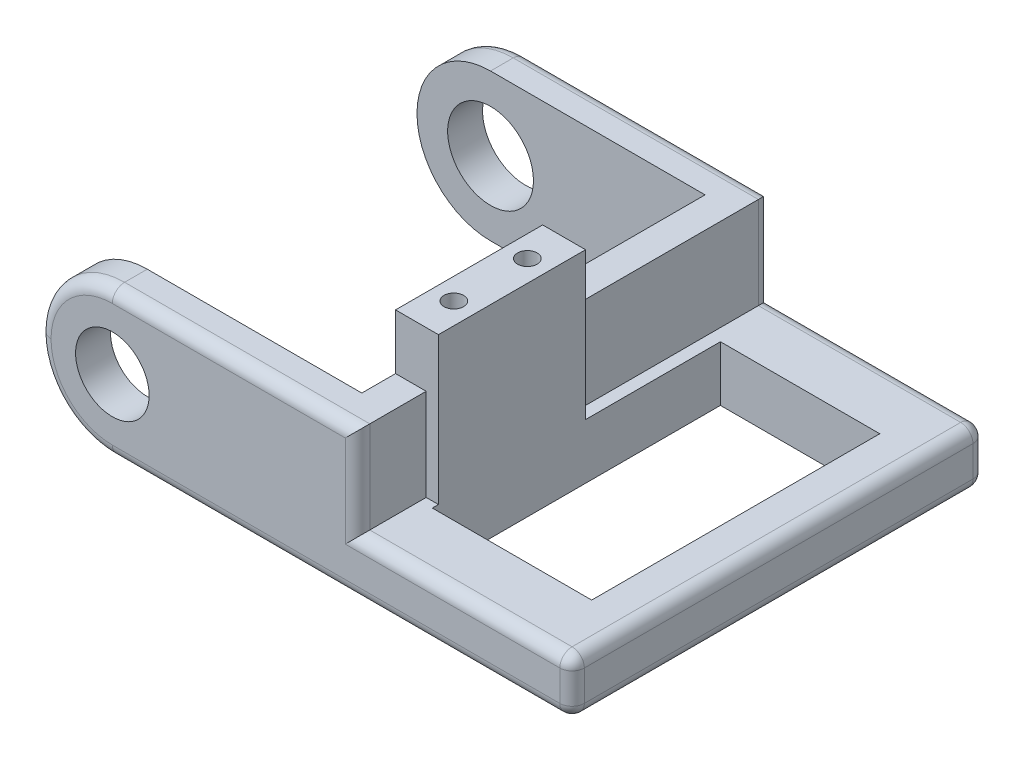
SolidWorks part; units mm, degrees
ref_plane "Front Plane" through (0, 0, 0) normal (0, 0, 1) x (1, 0, 0)
ref_plane "Top Plane" through (0, 0, 0) normal (0, 1, 0) x (1, 0, 0)
ref_plane "Right Plane" through (0, 0, 0) normal (1, 0, 0) x (0, 0, -1)
sketch "Sketch1" plane through (0, 0, 0) normal (1, 0, 0) x (0, 0, -1)
  line L0 (-222.6467, 45.44) -> (-222.6467, 62.0152) construction
  line L1 (-256.3467, 26.069) -> (-222.6467, 26.069)
  line L2 (-256.3467, 26.069) -> (-256.3467, 14.069)
  line L3 (-256.3467, 14.069) -> (-222.6467, 14.069)
  line L4 (-222.6467, 26.069) -> (-222.6467, 14.069)
  dimension "D1" = 12
  dimension "D2" = 33.7
  dimension "D3" = 0
extrude "Boss-Extrude1" add sketch "Sketch1" along normal blind 2.5
sketch "Sketch2" plane through (2.5, 0, 0) normal (1, 0, 0) x (0, 0, -1)
  line L0 (-222.6467, 14.069) -> (-222.6467, 26.069) construction
  line L1 (-256.3467, 14.069) -> (-222.6467, 14.069)
  line L2 (-256.3467, 14.069) -> (-256.3467, 18.569)
  line L3 (-256.3467, 18.569) -> (-222.6467, 18.569)
  line L4 (-222.6467, 14.069) -> (-222.6467, 18.569)
  dimension "D1" = 4.5
extrude "Boss-Extrude2" add sketch "Sketch2" along normal blind 17.5
sketch "Sketch3" plane through (0, 18.569, 0) normal (0, 1, 0) x (1, 0, 0)
  line L0 (2.5, -222.6467) -> (2.5, -256.3467) construction
  line L1 (3.5, -227.7467) -> (16.5, -227.7467)
  line L2 (3.5, -227.7467) -> (3.5, -251.2467)
  line L3 (3.5, -251.2467) -> (16.5, -251.2467)
  line L4 (16.5, -227.7467) -> (16.5, -251.2467)
  line L8 (20, -222.6467) -> (2.5, -222.6467) construction
  dimension "D1" = 1
  dimension "D2" = 23.5
  dimension "D3" = 5.1
  dimension "D4" = 13
extrude "Cut-Extrude1" cut sketch "Sketch3" against normal through all
sketch "Sketch4" plane through (0, 0, 0) normal (-1, 0, 0) x (0, 0, 1)
  line L0 (256.3467, 14.069) -> (222.6467, 14.069) construction
  line L1 (222.6467, 26.069) -> (225.4967, 26.069)
  line L2 (222.6467, 26.069) -> (222.6467, 14.069)
  line L3 (222.6467, 14.069) -> (225.4967, 14.069)
  line L4 (225.4967, 26.069) -> (225.4967, 14.069)
  line L6 (256.3467, 26.069) -> (253.4967, 26.069)
  line L7 (256.3467, 26.069) -> (256.3467, 14.069)
  line L8 (256.3467, 14.069) -> (253.4967, 14.069)
  line L9 (253.4967, 26.069) -> (253.4967, 14.069)
  dimension "D1" = 2.85
  dimension "D2" = 2.85
extrude "Boss-Extrude3" add sketch "Sketch4" along normal blind 23.5
fillet "Fillet1" radius 6 4 edges at (-23.5, 14.069, 224.0717) (-23.5, 26.069, 224.0717) (-23.5, 14.069, 254.9217) (-23.5, 26.069, 254.9217)
sketch "Sketch5" plane through (0, 0, 256.3467) normal (0, 0, 1) x (1, 0, 0)
  circle A0 centre (-17.5, 20.069) radius 3
extrude "Cut-Extrude2" cut sketch "Sketch5" against normal blind 4
sketch "Sketch6" plane through (0, 0, 225.4967) normal (0, 0, 1) x (1, 0, 0)
  circle A0 centre (-17.5, 20.069) radius 3.5
extrude "Cut-Extrude3" cut sketch "Sketch6" against normal blind 4
sketch "Sketch7" plane through (0, 18.569, 0) normal (0, 1, 0) x (1, 0, 0)
  line L0 (3.5, -227.7467) -> (3.5, -251.2467) construction
  line L1 (3.5, -238.7467) -> (0, -238.7467)
  line L2 (3.5, -238.7467) -> (3.5, -250.7467)
  line L3 (3.5, -250.7467) -> (0, -250.7467)
  line L4 (0, -238.7467) -> (0, -250.7467)
  line L5 (0, -225.4967) -> (0, -253.4967) construction
  line L8 (3.5, -238.7467) -> (0, -238.7467) construction
  line L9 (0, -250.7467) -> (3.5, -250.7467) construction
  dimension "D1" = 0
  dimension "D2" = 0
extrude "Boss-Extrude4" add sketch "Sketch7" along normal blind 12
fillet "Fillet2" radius 1 16 edges at (-7.5, 26.069, 256.3467) (-21.7426, 24.3116, 256.3467) (-21.7426, 15.8263, 256.3467) (-7.5, 26.069, 222.6467) (-21.7426, 24.3116, 222.6467) (-21.7426, 15.8263, 222.6467) (2.5, 22.319, 222.6467) (2.5, 22.319, 256.3467) (1.25, 14.069, 256.3467) (1.25, 14.069, 222.6467) (20, 16.319, 222.6467) (11.25, 18.569, 222.6467) (20, 14.069, 239.4967) (20, 18.569, 239.4967) (20, 16.319, 256.3467) (11.25, 18.569, 256.3467)
sketch "Sketch8" plane through (0, 30.569, 0) normal (0, 1, 0) x (1, 0, 0)
  circle A0 centre (1.75, -247.7467) radius 0.8
  circle A1 centre (1.75, -241.7467) radius 0.8
extrude "Cut-Extrude4" cut sketch "Sketch8" against normal blind 2
